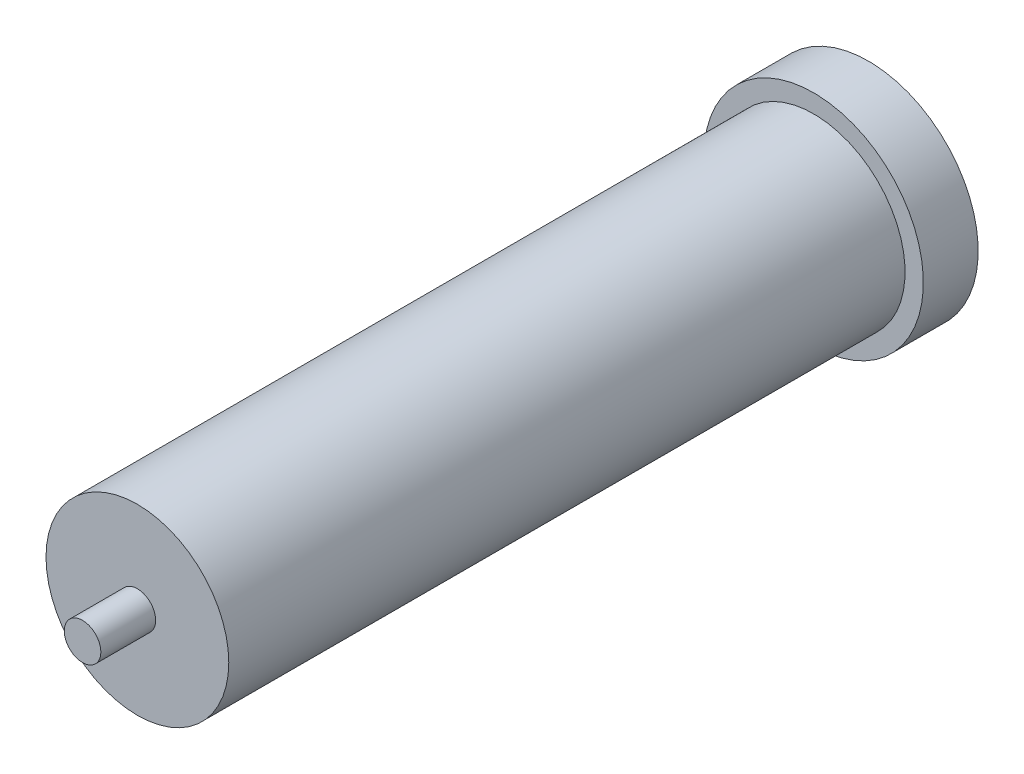
SolidWorks part; units mm, degrees
material "Сталь ШХ15 ГОСТ 801-78"
ref_plane "Plane1" through (0, 0, 0) normal (0, 0, 1) x (1, 0, 0)
ref_plane "Plane2" through (0, 0, 0) normal (0, 1, 0) x (1, 0, 0)
ref_plane "Plane3" through (0, 0, 0) normal (1, 0, 0) x (0, 0, -1)
sketch "Эскиз1" plane through (0, 0, 0) normal (0, 0, 1) x (1, 0, 0)
  circle A0 centre (0, 0) radius 5
  dimension "D1" = 10
extrude "Бобышка-Вытянуть1" add sketch "Эскиз1" along normal blind 40 contours A0
sketch "Эскиз2" plane through (0, 0, 40) normal (0, 0, 1) x (1, 0, 0)
  circle A0 centre (0, 0) radius 1
  dimension "D1" = 2
extrude "Бобышка-Вытянуть2" add sketch "Эскиз2" along normal blind 3 contours A0
sketch "Эскиз4" plane through (0, 0, 0) normal (0, 0, -1) x (-1, 0, 0)
  circle A0 centre (0, 0) radius 1
  dimension "D1" = 2
extrude "Бобышка-Вытянуть3" add sketch "Эскиз4" along normal blind 3
sketch "Эскиз6" plane through (0, 0, 0) normal (0, 0, -1) x (-1, 0, 0)
  circle A0 centre (0, 0) radius 6
  dimension "D1" = 12
extrude "Бобышка-Вытянуть5" add sketch "Эскиз6" against normal blind 3
